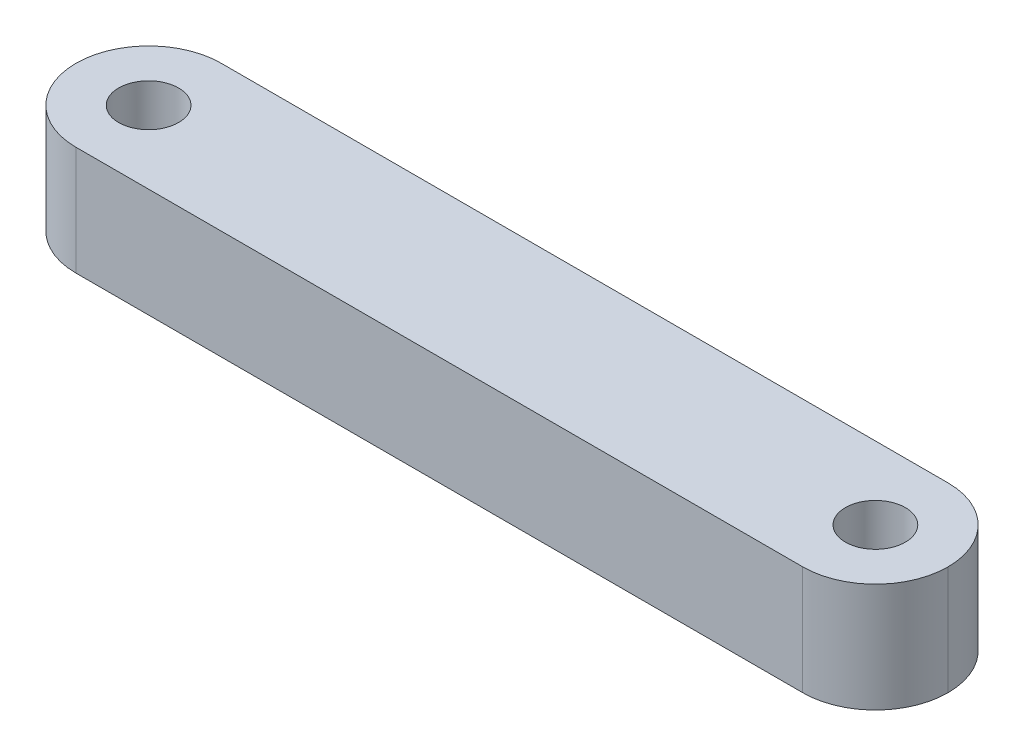
SolidWorks part; units mm, degrees
ref_plane "前视基准面" through (0, 0, 0) normal (0, 0, 1) x (1, 0, 0)
ref_plane "上视基准面" through (0, 0, 0) normal (0, 1, 0) x (1, 0, 0)
ref_plane "右视基准面" through (0, 0, 0) normal (1, 0, 0) x (0, 0, -1)
sketch "草图1" plane through (0, 0, 0) normal (0, 1, 0) x (1, 0, 0)
  line L1 (-24, 4) -> (24, 4)
  line L2 (-24, 4) -> (-24, -4)
  line L3 (-24, -4) -> (24, -4)
  line L4 (24, 4) -> (24, -4)
  line L5 (-24, 4) -> (24, -4) construction
  line L6 (-24, -4) -> (24, 4) construction
  point P0 (0, 0)
  dimension "D1" = 8
  dimension "D2" = 48
extrude "凸台-拉伸1" add sketch "草图1" along normal blind 6
sketch "草图2" plane through (0, 6, 0) normal (0, 1, 0) x (1, 0, 0)
  line L0 (24, -4) -> (24, 4) construction
  line L1 (0, -55) -> (0, 55) construction
  circle A0 centre (20, 0) radius 1.65
  circle A1 centre (-20, 0) radius 1.65
  dimension "D1" = 3.3
  dimension "D2" = 4
extrude "切除-拉伸1" cut sketch "草图2" against normal blind 15
fillet "圆角1" radius 4 4 edges at (-24, 3, 4) (-24, 3, -4) (24, 3, -4) (24, 3, 4)
